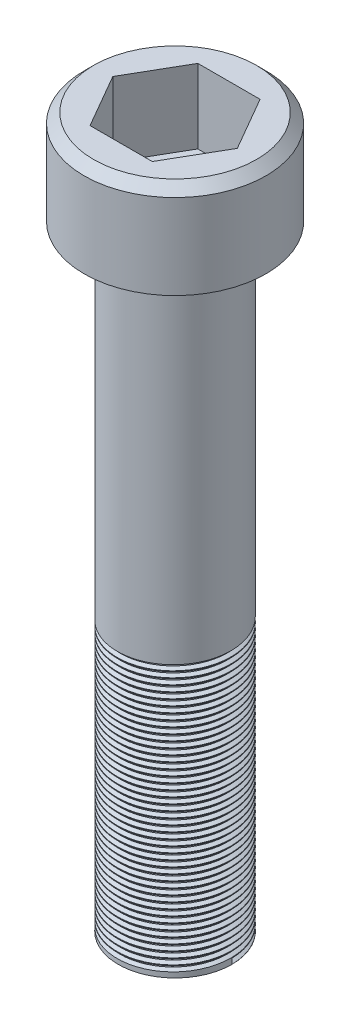
SolidWorks part; units mm, degrees
ref_plane "Płaszczyzna przednia" through (0, 0, 0) normal (0, 0, 1) x (1, 0, 0)
ref_plane "Płaszczyzna górna" through (0, 0, 0) normal (0, 1, 0) x (1, 0, 0)
ref_plane "Płaszczyzna prawa" through (0, 0, 0) normal (1, 0, 0) x (0, 0, -1)
sketch "Szkic1" plane through (0, 0, 0) normal (0, 1, 0) x (1, 0, 0)
  circle A0 centre (0, 0) radius 4.215
  dimension "D1" = 8.43
extrude "Dodanie-wyciągnięcie1" add sketch "Szkic1" along normal blind 52.65
sketch "Szkic2" plane through (0, 52.65, 0) normal (0, 1, 0) x (1, 0, 0)
  circle A0 centre (0, 0) radius 6.75
  dimension "D1" = 13.5
extrude "Dodanie-wyciągnięcie2" add sketch "Szkic2" against normal blind 7
sketch "Szkic3" plane through (0, 52.65, 0) normal (0, 1, 0) x (1, 0, 0)
  line L1 (-4.6188, 0) -> (-2.3094, -4)
  line L2 (-2.3094, -4) -> (2.3094, -4)
  line L3 (2.3094, -4) -> (4.6188, 0)
  line L4 (4.6188, 0) -> (2.3094, 4)
  line L5 (2.3094, 4) -> (-2.3094, 4)
  line L6 (-2.3094, 4) -> (-4.6188, 0)
  circle A0 centre (0, 0) radius 4 construction
  dimension "D1" = 8
extrude "Wytnij-wyciągnięcie1" cut sketch "Szkic3" against normal blind 5.5
chamfer "Sfazowanie1" distance 0.7 angle 45 1 edges at (0, 52.65, 6.75)
thread "Gwint1" pitch 0.45 method cut profile "Profil gwintu1" start angle 0, offset 0, length 20, pitch 0.45, diameter 8.43
ref_plane "Płaszczyzna1" through (4.215, 0, 0) normal (0, 0, 1) x (1, 0, 0)
sketch "Profil gwintu1" plane through (4.215, 0, 0) normal (0, 0, 1) x (1, 0, 0)
  line L0 (0, 0) -> (0, 0.45) construction
  line L11 (0, 0) -> (0, 0.3937)
  line L12 (0, 0.3937) -> (-0.2436, 0.2531)
  line L13 (-0.2436, 0.2531) -> (-0.2436, 0.1406)
  line L15 (-0.2436, 0.1406) -> (0, 0)
  line L17 (-0.2436, 0.1969) -> (0, 0.1969) construction
  point P2 (0, 0)
  dimension "Pitch" = 0.45
  dimension "Profile_Angle" = 60
  dimension "Profile_Land" = 0.1125
  dimension "Profile_Height" = 0.2436
